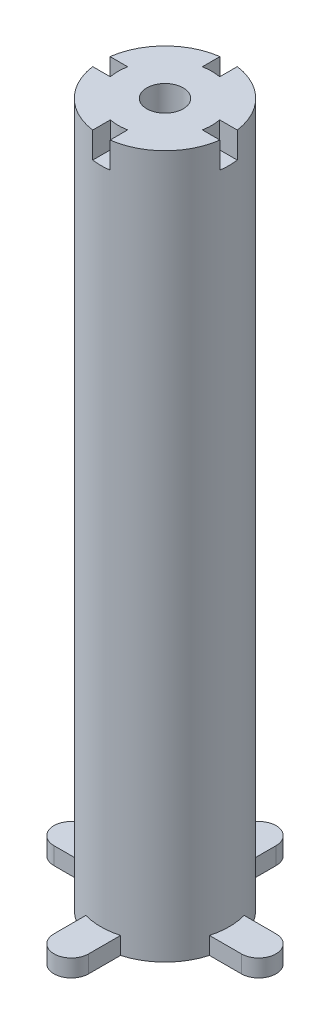
SolidWorks part; units mm, degrees
ref_plane "Front Plane" through (0, 0, 0) normal (0, 0, 1) x (1, 0, 0)
ref_plane "Top Plane" through (0, 0, 0) normal (0, 1, 0) x (1, 0, 0)
ref_plane "Right Plane" through (0, 0, 0) normal (1, 0, 0) x (0, 0, -1)
other "Configuration Table"
sketch "草图1" plane through (0, 0, 0) normal (0, 1, 0) x (1, 0, 0)
  circle A0 centre (0, 0) radius 7.4
  circle A1 centre (0, 0) radius 6
extrude "凸台-拉伸1" add sketch "草图1" along normal blind 78
sketch "草图2" plane through (0, 0, 0) normal (0, -1, 0) x (-1, 0, 0)
  circle A0 centre (0, 0) radius 6
extrude "凸台-拉伸2" add sketch "草图2" against normal blind 10
sketch "草图3" plane through (0, 0, 0) normal (0, -1, 0) x (1, 0, 0)
  line L0 (0, 0) -> (0, 7.4) construction
  line L1 (0, 5) -> (0, 10.8) construction
  line L10 (-2, 5) -> (-2, 10.8)
  line L11 (2, 5) -> (2, 10.8)
  line L14 (5, 0) -> (10.8, 0) construction
  line L17 (5, 2) -> (10.8, 2)
  line L20 (5, -2) -> (10.8, -2)
  line L21 (0, -5) -> (0, -10.8) construction
  line L24 (2, -5) -> (2, -10.8)
  line L27 (-2, -5) -> (-2, -10.8)
  line L30 (-5, 0) -> (-10.8, 0) construction
  line L31 (-5, -2) -> (-10.8, -2)
  line L32 (-5, 2) -> (-10.8, 2)
  circle A9 centre (0, 0) radius 7.4
  arc A10 (-2, 5) -> (2, 5) centre (0, 5) ccw
  arc A11 (2, 10.8) -> (-2, 10.8) centre (0, 10.8) ccw
  arc A24 (5, 2) -> (5, -2) centre (5, 0) ccw
  arc A25 (10.8, -2) -> (10.8, 2) centre (10.8, 0) ccw
  arc A26 (2, -5) -> (-2, -5) centre (0, -5) ccw
  arc A27 (-2, -10.8) -> (2, -10.8) centre (0, -10.8) ccw
  arc A28 (-5, -2) -> (-5, 2) centre (-5, 0) ccw
  arc A29 (-10.8, 2) -> (-10.8, -2) centre (-10.8, 0) ccw
  point P7 (0, 7.9)
  point P15 (7.9, 0)
  point P22 (0, -7.9)
  point P29 (-7.9, 0)
  point P35 (0.004, 0.5143)
  point P36 (0, 0)
  point P57 (0, 0)
  circle M10 centre (0, 0) radius 7.4
  dimension "D1" = 5
  dimension "D3" = 5.8
extrude "凸台-拉伸3" add sketch "草图3" against normal blind 2 contours L11 A11 L10 M10 | L32 A29 L31 M10 | L20 A25 L17 M10 | L27 A27 L24 M10 region at (0, 0, 9.8589) region at (-9.8589, 0, 0) region at (9.8589, 0, 0) region at (0, 0, -9.8589)
sketch "草图4" plane through (0, 0, 0) normal (0, -1, 0) x (1, 0, 0)
  circle A0 centre (0, 0) radius 2.1
extrude "切除-拉伸1" cut sketch "草图4" against normal through all
sketch "草图7" plane through (0, 78, 0) normal (0, 1, 0) x (1, 0, 0)
  circle A0 centre (0, 0) radius 7.4
extrude "凸台-拉伸4" add sketch "草图7" along normal blind 3 and the other way blind 10
sketch "草图10" plane through (0, 68, 0) normal (0, -1, 0) x (1, 0, 0)
  line L0 (0, 6) -> (0, -6)
  arc A0 (0, 6) -> (0, -6) centre (0, 0) ccw
revolve "切除-旋转15" cut sketch "草图10" angle 360 about L0 region at (-2.5465, 68, 0)
sketch "草图11" plane through (0, 81, 0) normal (0, 1, 0) x (1, 0, 0)
  circle A0 centre (0, 0) radius 2.1
extrude "切除-拉伸2" cut sketch "草图11" against normal blind 15
sketch "草图12" plane through (0, 81, 0) normal (0, 1, 0) x (1, 0, 0)
  line L0 (0, 0) -> (0, 7.4) construction
  line L1 (5.4, 1) -> (5.3066, 1)
  line L2 (-1, 5.4) -> (-1, 7.3321)
  line L3 (-1, 5.4) -> (-1, 5.3066)
  line L4 (1, 5.4) -> (1, 7.3321)
  line L5 (1, 5.4) -> (1, 5.3066)
  line L6 (5.4, 1) -> (7.3321, 1)
  line L7 (5.4, -1) -> (7.3321, -1)
  line L8 (5.4, -1) -> (5.3066, -1)
  line L9 (1, -5.4) -> (1, -5.3066)
  line L10 (1, -5.4) -> (1, -7.3321)
  line L11 (-1, -5.4) -> (-1, -7.3321)
  line L12 (-1, -5.4) -> (-1, -5.3066)
  line L13 (-5.4, -1) -> (-5.3066, -1)
  line L14 (-5.4, -1) -> (-7.3321, -1)
  line L15 (-5.4, 1) -> (-7.3321, 1)
  line L16 (-5.4, 1) -> (-5.3066, 1)
  arc A0 (2, 7.1246) -> (-2, 7.1246) centre (0, 0) ccw construction
  arc A1 (1, 7.3321) -> (-1, 7.3321) centre (0, 0) ccw
  arc A2 (1, 5.3066) -> (-1, 5.3066) centre (0, 0) ccw
  arc A3 (5.3066, -1) -> (5.3066, 1) centre (0, 0) ccw
  arc A4 (7.3321, -1) -> (7.3321, 1) centre (0, 0) ccw
  arc A5 (-1, -5.3066) -> (1, -5.3066) centre (0, 0) ccw
  arc A6 (-1, -7.3321) -> (1, -7.3321) centre (0, 0) ccw
  arc A7 (-5.3066, 1) -> (-5.3066, -1) centre (0, 0) ccw
  arc A8 (-7.3321, 1) -> (-7.3321, -1) centre (0, 0) ccw
  point P10 (0, 5.4)
  point P12 (0, 5.4)
  point P35 (0, 0)
  dimension "D1" = 2
  dimension "D2" = 4
extrude "切除-拉伸3" cut sketch "草图12" against normal blind 3
